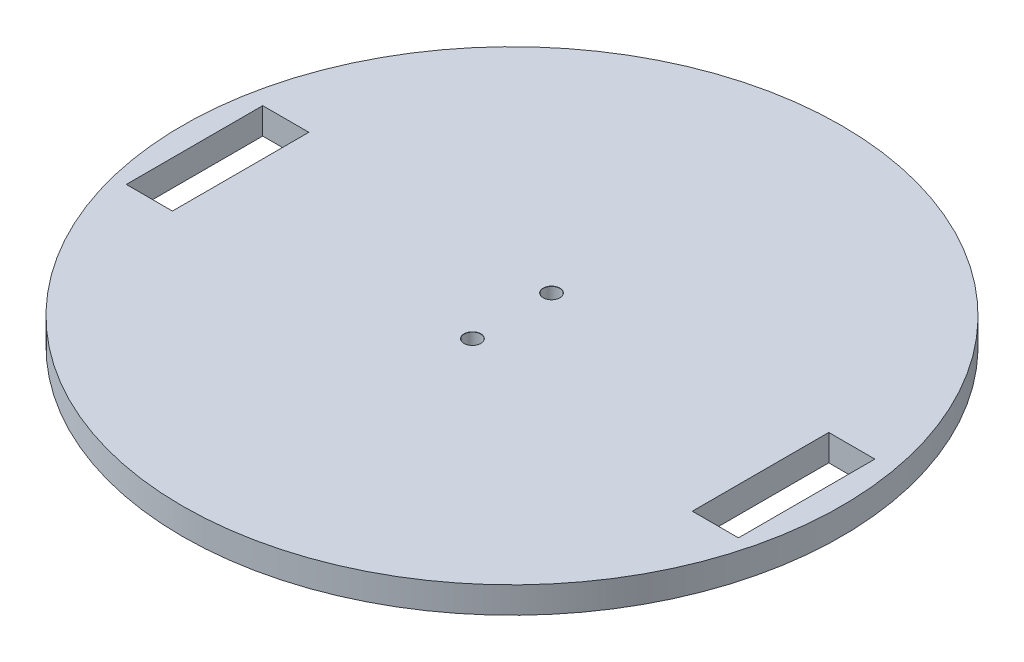
SolidWorks part; units mm, degrees
ref_plane "Front Plane" through (0, 0, 0) normal (0, 0, 1) x (1, 0, 0)
ref_plane "Top Plane" through (0, 0, 0) normal (0, 1, 0) x (1, 0, 0)
ref_plane "Right Plane" through (0, 0, 0) normal (1, 0, 0) x (0, 0, -1)
sketch "Sketch2" plane through (0, 0, 0) normal (0, 1, 0) x (1, 0, 0)
  line L0 (0, 50) -> (0, -40.0556) construction
  line L1 (-33.4012, 8.7) -> (-26.4012, 8.7)
  line L2 (-33.4012, 8.7) -> (-33.4012, -12)
  line L3 (-33.4012, -12) -> (-26.4012, -12)
  line L4 (-26.4012, 8.7) -> (-26.4012, -12)
  line L5 (33.4012, -12) -> (26.4012, -12)
  line L6 (33.4012, 8.7) -> (33.4012, -12)
  line L7 (26.4012, 8.7) -> (26.4012, -12)
  line L8 (33.4012, 8.7) -> (26.4012, 8.7)
  circle A0 centre (0, 0) radius 50
  dimension "D1" = 100
  dimension "D4" = 12
  dimension "D2" = 7
  dimension "D3" = 20.7
extrude "Boss-Extrude2" add sketch "Sketch2" along normal blind 4
hole_wizard "Tap Drill for M3x0.5 Tap1" positions "Sketch3" profile "Sketch4" hole size "M3x0.5" standard "ANSI Metric" end condition through all
sketch "Sketch3" plane through (0, 4, 0) normal (0, 1, 0) x (1, 0, 0)
  point P0 (0, 6)
  point P2 (0, -6)
  dimension "D1" = 6
  dimension "D2" = 6
sketch "Sketch4" plane through (0, 4, -6) normal (1, 0, 0) x (0, 0, 1)
  line L0 (0, 0) -> (0, 4)
  line L1 (0, 4) -> (1.25, 4)
  line L2 (1.25, 4) -> (1.25, 0.025)
  line L3 (1.25, 0.025) -> (1.275, 0)
  line L5 (1.275, 0) -> (0, 0)
  line L6 (-1.25, 0.025) -> (-1.275, 0) construction
  line L11 (0, -6.35) -> (0, 107.95) construction
  dimension "Thru Hole Dia." = 2.5
  dimension "Thru Hole Depth" = 4
  dimension "Near C'Sink Dia." = 2.55
  dimension "Near C'Sink Angle" = 90
sketch "Sketch5" plane through (0, 0, 0) normal (0, -1, 0) x (1, 0, 0)
  line L0 (-33.4012, -8.7) -> (-39.5198, -8.7)
  line L1 (33.4012, -8.7) -> (39.357, -8.7)
  line L2 (-26.4012, 12) -> (-26.4012, -8.7) construction
  line L3 (-39.5198, -8.7) -> (-46.5198, -8.7)
  line L4 (-39.5198, -8.7) -> (-39.5198, 12)
  line L5 (-39.5198, 12) -> (-46.5198, 12)
  line L6 (-46.5198, -8.7) -> (-46.5198, 12)
  line L7 (-33.4012, 12) -> (-26.4012, 12) construction
  line L9 (39.357, -8.7) -> (46.357, -8.7)
  line L10 (39.357, -8.7) -> (39.357, 12)
  line L11 (39.357, 12) -> (46.357, 12)
  line L12 (46.357, -8.7) -> (46.357, 12)
  line L13 (-36.5742, 14.9082) -> (-22.5115, 14.9082)
  line L14 (-36.5742, 14.9082) -> (-36.5742, -15.2604)
  line L15 (-36.5742, -15.2604) -> (-22.5115, -15.2604)
  line L16 (-22.5115, 14.9082) -> (-22.5115, -15.2604)
  line L17 (19.7252, 19.5839) -> (36.135, 19.5839)
  line L18 (19.7252, 19.5839) -> (19.7252, -17.1492)
  line L19 (19.7252, -17.1492) -> (36.135, -17.1492)
  line L20 (36.135, 19.5839) -> (36.135, -17.1492)
  line M8 (-33.4012, -8.7) -> (-33.4012, 12)
  line M9 (-33.4012, 12) -> (-26.4012, 12)
  line M10 (-26.4012, 12) -> (-26.4012, -8.7)
  line M11 (-26.4012, -8.7) -> (-33.4012, -8.7)
  line M13 (33.4012, 12) -> (33.4012, -8.7)
  line M14 (33.4012, -8.7) -> (26.4012, -8.7)
  line M15 (26.4012, -8.7) -> (26.4012, 12)
  line M16 (26.4012, 12) -> (33.4012, 12)
  dimension "D1" = 90
  dimension "D2" = 7
  dimension "D3" = 20.7
  dimension "D4" = 7
extrude "Boss-Extrude4" add sketch "Sketch5" against normal up to surface (4 mm away) contours M8 M11 M10 M9 | M13 M16 M15 M14 region at (-29.9012, 0, 1.65) region at (29.9012, 0, 1.65) up to face at (0, 4, -4.725)
extrude "Cut-Extrude1" cut sketch "Sketch5<4>" against normal blind 10 contours L6 L3 L4 L5 | L9 L12 L11 L10 region at (-43.0198, 0, 1.65) region at (42.857, 0, 1.65)
sketch "Sketch5<4>" plane through (0, 0, 0) normal (0, -1, 0) x (1, 0, 0) same geometry as "Sketch5"
